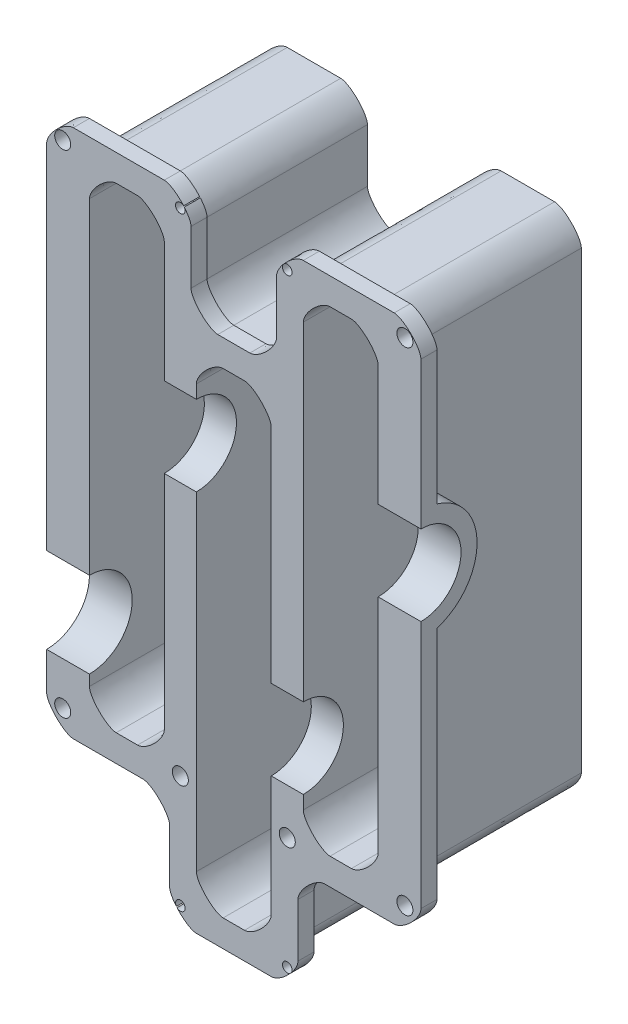
SolidWorks part; units mm, degrees
ref_plane "Front" through (0, 0, 0) normal (0, 0, 1) x (1, 0, 0)
ref_plane "Top" through (0, 0, 0) normal (0, 1, 0) x (1, 0, 0)
ref_plane "Right" through (0, 0, 0) normal (1, 0, 0) x (0, 0, -1)
sketch "Sketch1" plane through (0, 0, 0) normal (0, 0, 1) x (1, 0, 0)
  line L1 (-35, -59.5) -> (35, -59.5)
  line L2 (-35, -59.5) -> (-35, 59.5)
  line L3 (-35, 59.5) -> (35, 59.5)
  line L4 (35, -59.5) -> (35, 59.5)
  line L5 (-35, -59.5) -> (35, 59.5) construction
  line L6 (-35, 59.5) -> (35, -59.5) construction
  point P0 (0, 0)
  dimension "D1" = 70
  dimension "D2" = 119
extrude "Boss-Extrude1" add sketch "Sketch1" along normal blind 35
sketch "Sketch2" plane through (-35, 0, 0) normal (-1, 0, 0) x (0, 0, 1)
  line L0 (35, 59.5) -> (35, -59.5) construction
  line L1 (35, -59.5) -> (0, -59.5) construction
  circle A0 centre (35, -19.5) radius 8
  dimension "D1" = 16
  dimension "D2" = 40
extrude "Cut-Extrude1" cut sketch "Sketch2" against normal blind 8
sketch "Sketch3" plane through (0, 0, 35) normal (0, 0, 1) x (1, 0, 0)
  line L0 (-35, 59.5) -> (-35, -11.5) construction
  line L1 (-27, 54.5) -> (-13, 54.5)
  line L2 (-27, 54.5) -> (-27, -34.5)
  line L3 (-27, -34.5) -> (-13, -34.5)
  line L4 (-13, 54.5) -> (-13, 27)
  line L5 (-7, 34.5) -> (7, 34.5)
  line L6 (-7, 34.5) -> (-7, 27)
  line L7 (-7, -54.5) -> (7, -54.5)
  line L8 (7, 34.5) -> (7, -12)
  line L9 (13, 54.5) -> (27, 54.5)
  line L10 (13, 54.5) -> (13, -12)
  line L11 (13, -34.5) -> (27, -34.5)
  line L12 (27, 54.5) -> (27, -34.5)
  line L13 (-35, -19.5) -> (35, -19.5) construction
  line L14 (-35, -11.5) -> (-35, -27.5) construction
  line L15 (35, -59.5) -> (35, 59.5) construction
  line L16 (-35, 19.5) -> (35, 19.5) construction
  line L17 (-13, 27) -> (-7, 27)
  line L18 (-13, 12) -> (-7, 12)
  line L19 (-13, 12) -> (-13, -34.5)
  line L20 (-7, 12) -> (-7, -54.5)
  line L21 (7, -27) -> (13, -27)
  line L22 (7, -12) -> (13, -12)
  line L23 (7, -27) -> (7, -54.5)
  line L24 (13, -27) -> (13, -34.5)
  dimension "D1" = 8
  dimension "D2" = 14
  dimension "D3" = 6
  dimension "D4" = 6
  dimension "D5" = 15
  dimension "D6" = 39
  dimension "D7" = 89
  dimension "D8" = 15
  dimension "D9" = 7.5
  dimension "D10" = 15
  dimension "D11" = 7.5
  dimension "D12" = 15
  dimension "D13" = 89
  dimension "D14" = 8
extrude "Cut-Extrude2" cut sketch "Sketch3" against normal blind 32
sketch "Sketch4" plane through (35, 0, 0) normal (1, 0, 0) x (0, 0, -1)
  line L0 (-35, -59.5) -> (-35, 59.5) construction
  line L1 (-35, -59.5) -> (0, -59.5) construction
  circle A0 centre (-35, 19.5) radius 7.5
  dimension "D1" = 15
  dimension "D2" = 79
extrude "Cut-Extrude3" cut sketch "Sketch4" against normal blind 8
sketch "Sketch5" plane through (0, 0, 35) normal (0, 0, 1) x (1, 0, 0)
  line L0 (35, 59.5) -> (-35, 59.5) construction
  line L1 (-8, 39.5) -> (8, 39.5)
  line L2 (-8, 39.5) -> (-8, 59.5)
  line L3 (-8, 59.5) -> (8, 59.5)
  line L4 (8, 39.5) -> (8, 59.5)
  line L5 (-35, -59.5) -> (35, -59.5) construction
  line L6 (-12, -59.5) -> (-35, -59.5)
  line L7 (-12, -59.5) -> (-12, -39.5)
  line L8 (-12, -39.5) -> (-35, -39.5)
  line L9 (-35, -59.5) -> (-35, -39.5)
  line L10 (-35, -27.5) -> (-35, -59.5) construction
  line L11 (35, -59.5) -> (35, 12) construction
  line L12 (12, -59.5) -> (35, -59.5)
  line L13 (12, -59.5) -> (12, -39.5)
  line L14 (12, -39.5) -> (35, -39.5)
  line L15 (35, -59.5) -> (35, -39.5)
  line L16 (13, -34.5) -> (27, -34.5) construction
  line L17 (7, -54.5) -> (7, -27) construction
  line L18 (-27, -34.5) -> (-13, -34.5) construction
  line L19 (-7, 12) -> (-7, -54.5) construction
  line L20 (-13, 27) -> (-13, 54.5) construction
  line L21 (13, 54.5) -> (13, -12) construction
  line L22 (7, 34.5) -> (-7, 34.5) construction
  dimension "D1" = 5
  dimension "D2" = 5
  dimension "D3" = 5
  dimension "D4" = 5
  dimension "D5" = 5
  dimension "D6" = 5
  dimension "D7" = 5
extrude "Cut-Extrude4" cut sketch "Sketch5" against normal through all
sketch "Sketch7" plane through (-35, 0, 0) normal (-1, 0, 0) x (0, 0, 1)
  line L2 (32, 59.5) -> (0, 59.5)
  line L3 (0, 59.5) -> (0, -39.5)
  line L4 (32, -30.083) -> (32, -39.5)
  line L5 (32, 59.5) -> (32, -8.917)
  line L6 (32, -30.083) -> (32, -39.5)
  line L7 (32, 59.5) -> (32, -8.917)
  line L8 (0, -39.5) -> (32, -39.5)
  arc A2 (32, -8.917) -> (32, -30.083) centre (35, -19.5) ccw
  arc A3 (32, -8.917) -> (32, -30.083) centre (35, -19.5) ccw
  dimension "D1" = 3
extrude "Cut-Extrude5" cut sketch "Sketch7" against normal blind 5
sketch "Sketch8" plane through (0, -39.5, 0) normal (0, -1, 0) x (1, 0, 0)
  line L1 (-30, 32) -> (-12, 32)
  line L2 (-30, 32) -> (-30, 0)
  line L3 (-30, 0) -> (-12, 0)
  line L4 (-12, 32) -> (-12, 0)
extrude "Cut-Extrude6" cut sketch "Sketch8" against normal blind 2
sketch "Sketch9" plane through (-12, 0, 0) normal (-1, 0, 0) x (0, 0, 1)
  line L1 (32, -37.5) -> (0, -37.5)
  line L2 (32, -37.5) -> (32, -59.5)
  line L3 (32, -59.5) -> (0, -59.5)
  line L4 (0, -37.5) -> (0, -59.5)
extrude "Cut-Extrude7" cut sketch "Sketch9" against normal blind 2
sketch "Sketch10" plane through (0, -59.5, 0) normal (0, -1, 0) x (1, 0, 0)
  line L1 (-10, 32) -> (12, 32)
  line L2 (-10, 32) -> (-10, 0)
  line L3 (-10, 0) -> (12, 0)
  line L4 (12, 32) -> (12, 0)
extrude "Cut-Extrude8" cut sketch "Sketch10" against normal blind 2
sketch "Sketch11" plane through (12, 0, 0) normal (1, 0, 0) x (0, 0, -1)
  line L1 (-32, -57.5) -> (0, -57.5)
  line L2 (-32, -57.5) -> (-32, -39.5)
  line L3 (-32, -39.5) -> (0, -39.5)
  line L4 (0, -57.5) -> (0, -39.5)
extrude "Cut-Extrude9" cut sketch "Sketch11" against normal blind 2
sketch "Sketch12" plane through (0, -39.5, 0) normal (0, -1, 0) x (1, 0, 0)
  line L1 (10, 32) -> (35, 32)
  line L2 (10, 32) -> (10, 0)
  line L3 (10, 0) -> (35, 0)
  line L4 (35, 32) -> (35, 0)
extrude "Cut-Extrude10" cut sketch "Sketch12" against normal blind 2
sketch "Sketch13" plane through (35, 0, 0) normal (1, 0, 0) x (0, 0, -1)
  line L0 (0, -37.5) -> (-32, -37.5)
  line L1 (0, -37.5) -> (-32, -37.5) construction
  line L2 (-32, 59.5) -> (0, 59.5)
  line L3 (0, 59.5) -> (0, -37.5)
  line L4 (-32, 29.5623) -> (-32, 59.5)
  line L5 (-32, -39.5) -> (-32, 9.4377)
  line L6 (-32, 29.5623) -> (-32, 59.5)
  line L7 (-32, -37.5) -> (-32, 9.4377)
  line L8 (0, -37.5) -> (0, 59.5) construction
  arc A2 (-32, 9.4377) -> (-32, 29.5623) centre (-35, 19.5) ccw
  arc A3 (-32, 9.4377) -> (-32, 29.5623) centre (-35, 19.5) ccw
  dimension "D1" = 3
extrude "Cut-Extrude11" cut sketch "Sketch13" against normal blind 5
sketch "Sketch14" plane through (0, 59.5, 0) normal (0, 1, 0) x (1, 0, 0)
  line L1 (30, -32) -> (8, -32)
  line L2 (30, -32) -> (30, 0)
  line L3 (30, 0) -> (8, 0)
  line L4 (8, -32) -> (8, 0)
extrude "Cut-Extrude12" cut sketch "Sketch14" against normal blind 2
sketch "Sketch15" plane through (0, 59.5, 0) normal (0, 1, 0) x (1, 0, 0)
  line L1 (-30, -32) -> (-8, -32)
  line L2 (-30, -32) -> (-30, 0)
  line L3 (-30, 0) -> (-8, 0)
  line L4 (-8, -32) -> (-8, 0)
extrude "Cut-Extrude13" cut sketch "Sketch15" against normal blind 2
sketch "Sketch16" plane through (0, 39.5, 0) normal (0, 1, 0) x (1, 0, 0)
  line L1 (8, -32) -> (-8, -32)
  line L2 (8, -32) -> (8, 0)
  line L3 (8, 0) -> (-8, 0)
  line L4 (-8, -32) -> (-8, 0)
extrude "Cut-Extrude14" cut sketch "Sketch16" against normal blind 2
sketch "Sketch17" plane through (8, 0, 0) normal (-1, 0, 0) x (0, 0, 1)
  line L0 (32, 37.5) -> (0, 37.5) construction
  line L1 (32, 37.5) -> (0, 37.5)
  line L2 (32, 37.5) -> (32, 57.5)
  line L3 (32, 57.5) -> (0, 57.5)
  line L4 (0, 37.5) -> (0, 57.5)
extrude "Cut-Extrude15" cut sketch "Sketch17" against normal blind 2
sketch "Sketch18" plane through (-8, 0, 0) normal (1, 0, 0) x (0, 0, -1)
  line L1 (-32, 57.5) -> (0, 57.5)
  line L2 (-32, 57.5) -> (-32, 37.5)
  line L3 (-32, 37.5) -> (0, 37.5)
  line L4 (0, 57.5) -> (0, 37.5)
extrude "Cut-Extrude17" cut sketch "Sketch18" against normal blind 2
fillet "Fillet3" radius 5 3 edges at (13, 54.5, 19) (-7, 34.5, 19) (-27, 54.5, 19) conic radius 10
fillet "Fillet5" radius 5 3 edges at (27, 54.5, 19) (7, 34.5, 19) (-13, 54.5, 19) conic radius 10
fillet "Fillet6" radius 5 6 edges at (27, -34.5, 19) (13, -34.5, 19) (7, -54.5, 19) (-7, -54.5, 19) (-13, -34.5, 19) (-27, -34.5, 19) conic radius 10
fillet "Fillet7" radius 5 12 edges at (-10, 57.5, 16) (-30, 57.5, 16) (-30, -37.5, 16) (-10, -37.5, 16) (-10, -57.5, 16) (10, -57.5, 16) (10, -37.5, 16) (30, 57.5, 16) (10, 57.5, 16) (10, 37.5, 16) (-10, 37.5, 16) (30, -37.5, 16) conic radius 10
fillet "Fillet11" radius 5 1 edges at (35, -39.5, 33.5) conic radius 10
fillet "Fillet12" radius 5 11 edges at (-8, 39.5, 33.5) (-35, 59.5, 33.5) (-8, 59.5, 33.5) (8, 39.5, 33.5) (8, 59.5, 33.5) (35, 59.5, 33.5) (-35, -39.5, 33.5) (12, -39.5, 33.5) (-12, -39.5, 33.5) (-12, -59.5, 33.5) (12, -59.5, 33.5) conic radius 10
sketch "Sketch19" plane through (0, 0, 35) normal (0, 0, 1) x (1, 0, 0)
  line L0 (-13, 59.5) -> (-30, 59.5) construction
  line L1 (-32, 56.5) -> (32, 56.5) construction
  line L2 (-32, 56.5) -> (-32, -35.5) construction
  line L3 (-32, -35.5) -> (32, -35.5) construction
  line L4 (32, 56.5) -> (32, -35.5) construction
  line L5 (-35, 54.5) -> (-35, -11.5) construction
  line L6 (-7, 12) -> (-7, -49.5) construction
  line L7 (7, -49.5) -> (7, -27) construction
  circle A0 centre (-32, 56.5) radius 1.5
  circle A1 centre (32, 56.5) radius 1.5
  circle A2 centre (32, -35.5) radius 1.5
  circle A3 centre (-32, -35.5) radius 1.5
  circle A4 centre (-10, -35.5) radius 1.5
  circle A5 centre (10, -35.5) radius 1.5
  dimension "D5" = 3
  dimension "D7" = 3
  dimension "D1" = 92
  dimension "D2" = 64
  dimension "D3" = 3
  dimension "D4" = 3
  dimension "D6" = 3
extrude "Cut-Extrude18" cut sketch "Sketch19" against normal blind 10
sketch "Sketch20" plane through (0, 0, 35) normal (0, 0, 1) x (1, 0, 0)
  line L0 (-8, 54.5) -> (-8, 44.5) construction
  line L1 (-10, 56.5) -> (10, 56.5) construction
  line L2 (-10, 56.5) -> (-10, -56.5) construction
  line L3 (-10, -56.5) -> (10, -56.5) construction
  line L4 (10, 56.5) -> (10, -56.5) construction
  line L5 (-13, 59.5) -> (-30, 59.5) construction
  circle A0 centre (-10, 56.5) radius 0.9
  circle A1 centre (10, 56.5) radius 0.9
  circle A2 centre (10, -56.5) radius 0.9
  circle A3 centre (-10, -56.5) radius 0.9
  point P12 (0, 0)
  dimension "D5" = 1.8
  dimension "D1" = 113
  dimension "D2" = 20
  dimension "D3" = 2
  dimension "D4" = 3
extrude "Cut-Extrude19" cut sketch "Sketch20" against normal blind 10
sketch "Sketch22" plane through (-13, 0, 0) normal (-1, 0, 0) x (0, 0, 1)
  line L0 (35, 27) -> (3, 27)
  line L1 (3, 27) -> (3, 12)
  line L2 (3, 12) -> (35, 12)
  line L4 (3, 19.5) -> (52.1791, 19.5) construction
  arc A2 (35, 27) -> (35, 12) centre (35, 19.5) ccw
  dimension "D1" = 15
  dimension "D2" = 32
extrude "Boss-Extrude2" add sketch "Sketch22" against normal blind 6
sketch "Sketch23" plane through (13, 0, 0) normal (1, 0, 0) x (0, 0, -1)
  line L0 (-35, -12) -> (-3, -12)
  line L1 (-3, -12) -> (-3, -27)
  line L2 (-3, -27) -> (-35, -27)
  arc A0 (-35, -27) -> (-35, -12) centre (-35, -19.5) ccw
  dimension "D1" = 15
  dimension "D2" = 32
extrude "Boss-Extrude3" add sketch "Sketch23" against normal blind 6
